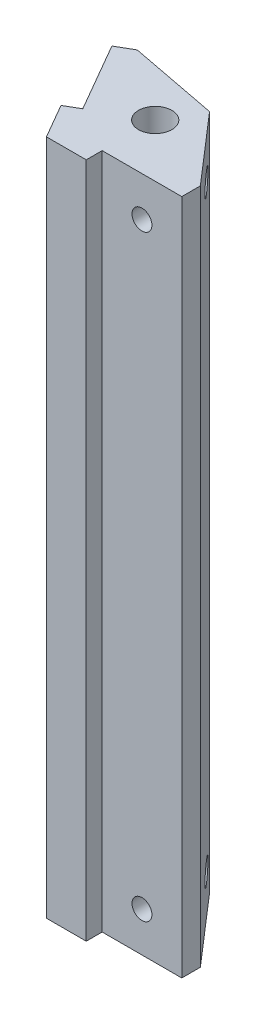
SolidWorks part; units mm, degrees
material "6061-T6 (SS)"
ref_plane "Front Plane" through (0, 0, 0) normal (0, 0, 1) x (1, 0, 0)
ref_plane "Top Plane" through (0, 0, 0) normal (0, 1, 0) x (1, 0, 0)
ref_plane "Right Plane" through (0, 0, 0) normal (1, 0, 0) x (0, 0, -1)
sketch "Sketch1" plane through (0, 0, 0) normal (0, 1, 0) x (1, 0, 0)
  line L0 (0, 0) -> (15, 0)
  line L1 (0, 0) -> (-7.5, 12.9904)
  line L2 (15, 0) -> (15, 4.3301)
  line L3 (0, 0) -> (2.5, 4.3301) construction
  line L6 (-3.75, 15.1554) -> (-7.5, 12.9904)
  line L7 (-3.75, 15.1554) -> (7.5, 12.9904)
  line L8 (7.5, 12.9904) -> (15, 4.3301)
  line L9 (2.5, 4.3301) -> (7.5, 12.9904) construction
  line L10 (-3.75, 15.1554) -> (2.5, 4.3301) construction
  line L11 (2.5, 4.3301) -> (15, 4.3301) construction
  dimension "D4" = 10
  dimension "D1" = 5
  dimension "D2" = 15
  dimension "D3" = 240
extrude "Boss-Extrude1" add sketch "Sketch1" along normal blind 85
sketch "Sketch3" plane through (0, 85, 0) normal (0, 1, 0) x (1, 0, 0)
  line L0 (-7.5, 12.9904) -> (-5.7679, 13.9904)
  line L1 (-3.75, 15.1554) -> (-7.5, 12.9904) construction
  line L2 (-5.7679, 13.9904) -> (-0.7679, 5.3301)
  line L3 (-0.7679, 5.3301) -> (-2.5, 4.3301)
  line L4 (-7.5, 12.9904) -> (0, 0) construction
  line L5 (-2.5, 4.3301) -> (-7.5, 12.9904)
  line L6 (15, 0) -> (15, 2)
  line L7 (15, 0) -> (15, 4.3301) construction
  line L8 (15, 2) -> (5, 2)
  line L9 (5, 2) -> (5, 0)
  line L11 (5, 0) -> (15, 0)
  line L12 (0, 0) -> (15, 0) construction
  dimension "D1" = 2
  dimension "D2" = 5
extrude "Cut-Extrude1" cut sketch "Sketch3" against normal through all
sketch "Sketch4" plane through (0, 85, 0) normal (0, 1, 0) x (1, 0, 0)
  line L0 (0, 0) -> (7.5, 12.9904) construction
  point P4 (5, 8.6603)
  dimension "D1" = 10
hole_wizard "M5x0.8 Tapped Hole1" positions "Sketch6" profile "Sketch7" tap size "M5x0.8" standard "ANSI Metric"
sketch "Sketch6" plane through (0, 85, 0) normal (0, 1, 0) x (1, 0, 0)
  point P0 (5, 8.6603)
sketch "Sketch7" plane through (5, 85, -8.6603) normal (1, 0, 0) x (0, 0, 1)
  line L0 (0, 0) -> (0, 17.2618)
  line L1 (0, 17.2618) -> (2.1, 16)
  line L2 (2.1, 16) -> (2.1, 0)
  line L5 (2.1, 0) -> (0, 0)
  line L10 (0, 17.2618) -> (-2.1, 16) construction
  line L11 (0, -6.35) -> (0, 107.95) construction
  dimension "Tap Drill Dia." = 4.2
  dimension "Tap Drill Depth" = 16
  dimension "Drill Angle" = 118
cosmetic thread "Hole Thread1" parameters "D1"=14, "D2"=5
ref_point "Point1"
hole_wizard "M5x0.8 Tapped Hole2" positions "Sketch11" profile "Sketch10" tap size "M5x0.8" standard "ANSI Metric"
sketch "Sketch11" plane through (0, 0, 0) normal (0, -1, 0) x (-1, 0, 0)
  point P0 (-5, 8.6603)
sketch "Sketch10" plane through (5, 0, -8.6603) normal (1, 0, 0) x (0, 0, -1)
  line L0 (0, 0) -> (0, 17.6618)
  line L1 (0, 17.6618) -> (2.1, 16.4)
  line L2 (2.1, 16.4) -> (2.1, 0)
  line L5 (2.1, 0) -> (0, 0)
  line L10 (0, 17.6618) -> (-2.1, 16.4) construction
  line L11 (0, -6.35) -> (0, 107.95) construction
  dimension "Tap Drill Dia." = 4.2
  dimension "Tap Drill Depth" = 16.4
  dimension "Drill Angle" = 118
cosmetic thread "Hole Thread2" parameters "D1"=14, "D2"=5
sketch "Sketch12" plane through (1.7321, 0, -1) normal (-0.866, 0, 0.5) x (0.5, 0, 0.866)
  line L0 (-15, 42.5) -> (-5, 42.5) construction
  line L1 (-15, 0) -> (-15, 85) construction
  line L2 (-5, 0) -> (-5, 85) construction
  line L3 (-10, 80) -> (-10, 5) construction
  point P8 (-10, 42.5)
  dimension "D1" = 75
hole_wizard "M3x0.5 Tapped Hole1" positions "Sketch14" profile "Sketch13" tap size "M3x0.5" standard "ANSI Metric" end condition through all
sketch "Sketch14" plane through (1.7321, 0, -1) normal (-0.866, 0, 0.5) x (0.5, 0, 0.866)
  point P0 (-10, 80)
  point P3 (-10, 5)
sketch "Sketch13" plane through (-3.2679, 80, -9.6603) normal (0, 1, 0) x (0.5, 0, 0.866)
  line L0 (0, 0) -> (0, 18.5681)
  line L1 (0, 18.5681) -> (1.25, 18.5681)
  line L2 (1.25, 18.5681) -> (1.25, 0)
  line L5 (1.25, 0) -> (0, 0)
  line L11 (0, -6.35) -> (0, 107.95) construction
  dimension "Thru Tap Drill Dia." = 2.5
  dimension "Thru Tap Drill Depth" = 18.5681
cosmetic thread "Hole Thread3" parameters "D2"=3
cosmetic thread "Hole Thread4" parameters "D2"=3
sketch "Sketch15" plane through (0, 0, -2) normal (0, 0, 1) x (1, 0, 0)
  line L0 (5, 42.5) -> (15, 42.5) construction
  line L1 (5, 0) -> (5, 85) construction
  line L2 (15, 0) -> (15, 85) construction
  line L3 (10, 80) -> (10, 5) construction
  point P8 (10, 42.5)
  dimension "D1" = 75
hole_wizard "M3x0.5 Tapped Hole2" positions "Sketch17" profile "Sketch16" tap size "M3x0.5" standard "ANSI Metric" end condition through all
sketch "Sketch17" plane through (0, 0, -2) normal (0, 0, 1) x (1, 0, 0)
  point P0 (10, 80)
  point P3 (10, 5)
sketch "Sketch16" plane through (10, 80, -2) normal (1, 0, 0) x (0, -1, 0)
  line L0 (0, 0) -> (0, 13.1554)
  line L1 (0, 13.1554) -> (1.25, 13.1554)
  line L2 (1.25, 13.1554) -> (1.25, 0)
  line L5 (1.25, 0) -> (0, 0)
  line L11 (0, -6.35) -> (0, 107.95) construction
  dimension "Thru Tap Drill Dia." = 2.5
  dimension "Thru Tap Drill Depth" = 13.1554
cosmetic thread "Hole Thread5" parameters "D2"=3
cosmetic thread "Hole Thread6" parameters "D2"=3
